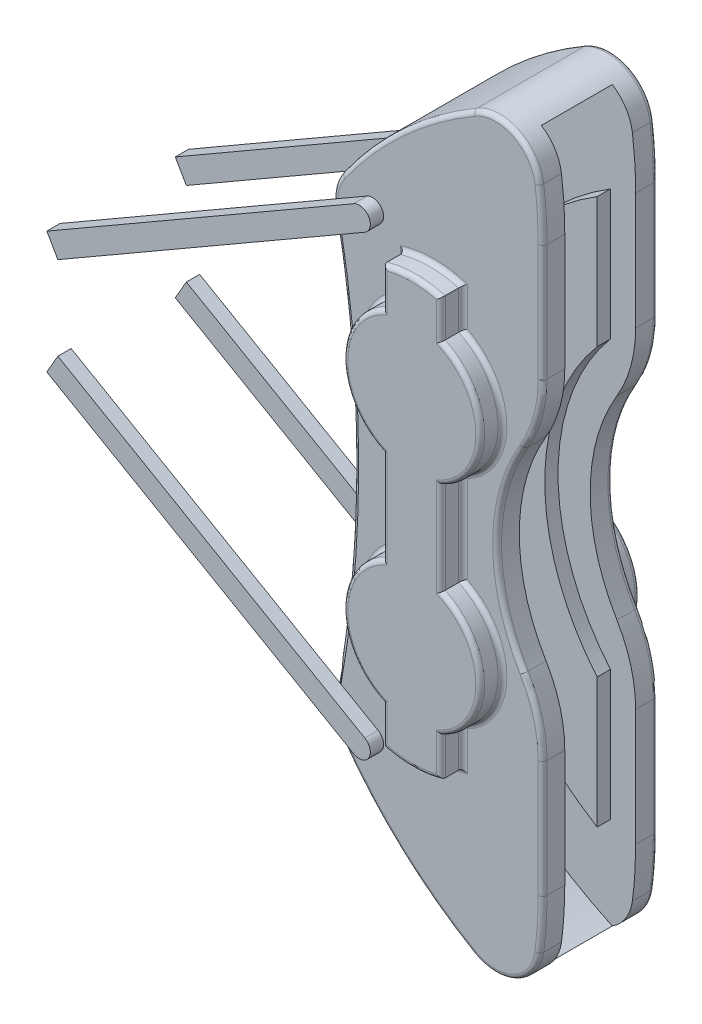
SolidWorks part; units mm, degrees
ref_plane "Ön Düzlem" through (0, 0, 0) normal (0, 0, 1) x (1, 0, 0)
ref_plane "Üst Düzlem" through (0, 0, 0) normal (0, 1, 0) x (1, 0, 0)
ref_plane "Sağ Düzlem" through (0, 0, 0) normal (1, 0, 0) x (0, 0, -1)
sketch "Çizim1" plane through (0, 0, 0) normal (0, 0, 1) x (1, 0, 0)
  line L0 (-32.4812, 27.8036) -> (-32.4812, 89.8036)
  line L1 (-32.4812, -27.8036) -> (-32.4812, -89.8036)
  circle A1 centre (0, 0) radius 85.977 construction
  arc A2 (-32.4812, 27.8036) -> (-32.4812, -27.8036) centre (0, 0) ccw
  arc A3 (-32.4812, 89.8036) -> (-32.4812, -89.8036) centre (0, 0) ccw
  dimension "D1" = 62
extrude "Yükseklik-Ekstrüzyon1" add sketch "Çizim1" along normal blind 5 from offset 13
extrude "Yükseklik-Ekstrüzyon2" add sketch "Çizim1<2>" against normal blind 5 from offset 13 separate body offset against normal yes
sketch "Çizim1<2>" plane through (0, 0, 0) normal (0, 0, 1) x (1, 0, 0) same geometry as "Çizim1"
sketch "Çizim2" plane through (0, 0, 0) normal (0, 0, 1) x (1, 0, 0)
  line L0 (-32.4812, 89.8036) -> (-32.4812, 84.4702)
  line L1 (-32.4812, -84.4702) -> (-32.4812, -89.8036)
  arc A0 (-32.4812, 89.8036) -> (-32.4812, -89.8036) centre (0, 0) ccw
  arc A1 (-32.4812, 84.4702) -> (-32.4812, -84.4702) centre (0, 0) ccw
  dimension "D1" = 181
extrude "Yükseklik-Ekstrüzyon3" add sketch "Çizim2" along normal mid plane 32
sketch "Çizim3" plane through (0, 0, 0) normal (0, 0, 1) x (1, 0, 0)
  arc A0 (-80.9899, 54.3972) -> (-80.9899, -54.3972) centre (-325, 0) cw
  arc A1 (-80.9899, 54.3972) -> (-80.9899, -54.3972) centre (0, 0) ccw
  dimension "D1" = 250
  dimension "D2" = 325
extrude "Kes-Ekstrüzyon1" cut sketch "Çizim3" against normal mid plane 36
sketch "Çizim4" plane through (0, 0, 0) normal (0, 0, 1) x (1, 0, 0)
  line L0 (-38.1773, 61.6339) -> (-38.1773, 32.2876)
  line L1 (-38.1773, -32.2876) -> (-38.1773, -61.6339)
  arc A0 (-38.1773, 32.2876) -> (-38.1773, -32.2876) centre (0, 0) ccw
  arc A1 (-38.1773, 61.6339) -> (-38.1773, -61.6339) centre (0, 0) ccw
  dimension "D1" = 100
  dimension "D2" = 145
extrude "padd1" add sketch "Çizim4" along normal blind 3 from offset 10
extrude "padd2" add sketch "Çizim4<2>" against normal blind 3 from offset 10 offset against normal yes
sketch "Çizim4<2>" plane through (0, 0, 0) normal (0, 0, 1) x (1, 0, 0) same geometry as "Çizim4"
sketch "Çizim5" plane through (0, 0, 0) normal (0, 0, 1) x (1, 0, 0)
  line L0 (-32.4812, 27.8036) -> (-32.4812, 89.8036) construction
  line L1 (-32.4812, 89.8036) -> (-32.4812, 63.6373)
  line L2 (0, 0) -> (122.0079, 0) construction
  line L3 (-32.4812, -89.8036) -> (-32.4812, -63.6373)
  arc A0 (-32.4812, 89.8036) -> (-36.0961, 88.4126) centre (0, 0) ccw
  arc A1 (-32.4812, -89.8036) -> (-36.0961, -88.4126) centre (0, 0) cw
  ellipse E0 centre (-132.7587, 42.5721) end of major axis (-51.7919, 116.1981) minor radius 87.9351 (-32.4812, 63.6373) -> (-36.0961, 88.4126) ccw
  ellipse E1 centre (-132.7587, -42.5721) end of major axis (-213.7255, 31.054) minor radius 87.9351 (-32.4812, -63.6373) -> (-36.0961, -88.4126) cw
extrude "Kes-Ekstrüzyon2" cut sketch "Çizim5" against normal mid plane 43
fillet "Radyus2" radius 10 4 edges at (-80.3765, 51.5687, 0) (-80.3765, -51.5687, 0) (-36.0961, -88.4126, 0) (-36.0961, 88.4126, 0)
fillet "Radyus3" radius 30 4 edges at (-32.4812, -27.8036, 15.5) (-32.4812, -27.8036, -15.5) (-32.4812, 27.8036, -15.5) (-32.4812, 27.8036, 15.5)
sketch "Çizim6" plane through (0, 0, 0) normal (0, 0, 1) x (1, 0, 0)
  line L0 (0, 0) -> (-100.0933, 0) construction
  line L1 (-57.0111, 83.6962) -> (-57.0111, -91.101) construction
  line L2 (-63.566, -10.4603) -> (-63.566, 10.4603)
  line L3 (-50.4561, 10.4603) -> (-50.4561, -10.4603)
  line L4 (-63.566, -38.456) -> (-63.566, -47.1335)
  line L6 (-50.4561, -47.1335) -> (-50.4561, -38.456)
  line L7 (-50.4561, 47.1335) -> (-50.4561, 38.456)
  line L8 (-63.566, 38.456) -> (-63.566, 47.1335)
  arc A1 (-50.4561, -10.4603) -> (-50.4561, -38.456) centre (-57.0111, -24.4582) cw
  arc A4 (-63.566, -38.456) -> (-63.566, -10.4603) centre (-57.0111, -24.4582) cw
  arc A5 (-63.566, -47.1335) -> (-50.4561, -47.1335) centre (-57.0111, -24.4582) ccw
  arc A6 (-63.566, 47.1335) -> (-50.4561, 47.1335) centre (-57.0111, 24.4582) cw
  arc A7 (-63.566, 38.456) -> (-63.566, 10.4603) centre (-57.0111, 24.4582) ccw
  arc A8 (-50.4561, 10.4603) -> (-50.4561, 38.456) centre (-57.0111, 24.4582) ccw
extrude "Yükseklik-Ekstrüzyon7" add sketch "Çizim6" along normal blind 5 from offset 18
extrude "Yükseklik-Ekstrüzyon8" add sketch "Çizim6<2>" against normal blind 5 from offset 18 offset against normal yes
sketch "Çizim6<2>" plane through (0, 0, 0) normal (0, 0, 1) x (1, 0, 0) same geometry as "Çizim6"
fillet "Radyus6" radius 1 76 edges at (-33.5598, 29.3045, -18) (-32.4812, 50.4568, -18) (-32.6664, 69.4272, -18) (-38.7346, 82.7968, -18) (-64.4946, 70.4283, -18) (-79.5205, 51.5608, -18) (-75, 0, -18) (-79.5205, -51.5608, -18) (-64.4946, -70.4283, -18) (-38.7346, -82.7968, -18) (-32.6664, -69.4272, -18) (-32.4812, -50.4568, -18) (-33.5598, -29.3045, -18) (-42.7559, 0, -18) (-41.5544, 24.4582, -18) (-50.4561, 0, -18) (-41.5544, -24.4582, -18) (-50.4561, -42.7948, -18) (-57.0111, -48.062, -18) (-63.566, -42.7948, -18) (-72.4677, -24.4582, -18) (-63.566, 0, -18) (-72.4677, 24.4582, -18) (-63.566, 42.7948, -18) (-57.0111, 48.062, -18) (-50.4561, 42.7948, -18) (-63.566, 42.7948, -23) (-72.4677, 24.4582, -23) (-63.566, 0, -23) (-72.4677, -24.4582, -23) (-63.566, -42.7948, -23) (-57.0111, -48.062, -23) (-50.4561, -42.7948, -23) (-41.5544, -24.4582, -23) (-50.4561, 0, -23) (-41.5544, 24.4582, -23) (-50.4561, 42.7948, -23) (-57.0111, 48.062, -23) (-50.4561, 42.7948, 23) (-41.5544, 24.4582, 23) (-50.4561, 0, 23) (-41.5544, -24.4582, 23) (-50.4561, -42.7948, 23) (-57.0111, -48.062, 23) (-63.566, -42.7948, 23) (-72.4677, -24.4582, 23) (-63.566, 0, 23) (-72.4677, 24.4582, 23) (-63.566, 42.7948, 23) (-57.0111, 48.062, 23) (-72.4677, 24.4582, 18) (-63.566, 0, 18) (-72.4677, -24.4582, 18) (-63.566, -42.7948, 18) (-57.0111, -48.062, 18) (-50.4561, -42.7948, 18) (-41.5544, -24.4582, 18) (-50.4561, 0, 18) (-41.5544, 24.4582, 18) (-50.4561, 42.7948, 18) (-57.0111, 48.062, 18) (-63.566, 42.7948, 18) (-32.6664, -69.4272, 18) (-38.7346, -82.7968, 18) (-64.4946, -70.4283, 18) (-79.5205, -51.5608, 18) (-75, 0, 18) (-79.5205, 51.5608, 18) (-64.4946, 70.4283, 18) (-38.7346, 82.7968, 18) (-32.6664, 69.4272, 18) (-32.4812, 50.4568, 18) (-33.5598, 29.3045, 18) (-42.7559, 0, 18) (-33.5598, -29.3045, 18) (-32.4812, -50.4568, 18)
sketch "Çizim8" plane through (0, 0, 0) normal (1, 0, 0) x (0, 0, -1)
  line L1 (-5, 97.3153) -> (-5, -107.4047)
  line L2 (-5, -107.4047) -> (43.4078, -107.4047)
  line L3 (43.4078, -107.4047) -> (43.4078, 97.3153)
  line L4 (43.4078, 97.3153) -> (-5, 97.3153)
extrude "Kes-Ekstrüzyon3" cut sketch "Çizim8" against normal blind 115 contours L4 L1 L2 L3
ref_plane "Düzlem2" through (0, 0, 5) normal (0, 0, -1) x (-1, 0, 0)
mirror "Aynalama3" about plane through (0, 0, 5) normal (0, 0, -1) of bodies 111
sketch "Çizim9" plane through (0, 0, 5) normal (0, 0, -1) x (-1, 0, 0)
  line L0 (0, 0) -> (158.417, 0) construction
  line L1 (138.901, 9.4365) -> (69.619, 49.4365)
  line L2 (141.401, 13.7666) -> (72.119, 53.7666)
  line L3 (141.401, 13.7666) -> (63.7255, 58.6125) construction
  line L4 (138.901, 9.4365) -> (61.2255, 54.2824) construction
  line L5 (138.901, 9.4365) -> (141.401, 13.7666)
  line L6 (138.901, -9.4365) -> (141.401, -13.7666)
  line L7 (141.401, -13.7666) -> (72.119, -53.7666)
  line L8 (138.901, -9.4365) -> (69.619, -49.4365)
  arc A0 (72.119, 53.7666) -> (69.619, 49.4365) centre (70.869, 51.6015) ccw
  arc A1 (72.119, -53.7666) -> (69.619, -49.4365) centre (70.869, -51.6015) cw
  dimension "D1" = 30
  dimension "D2" = 2.5
  dimension "D3" = 5
  dimension "D4" = 80
extrude "Yükseklik-Ekstrüzyon9" add sketch "Çizim9" along normal blind 3 from offset 16 offset against normal yes
extrude "Yükseklik-Ekstrüzyon10" add sketch "Çizim9<2>" along normal blind 3 from offset 13
sketch "Çizim9<2>" plane through (0, 0, 5) normal (0, 0, -1) x (-1, 0, 0) same geometry as "Çizim9"
